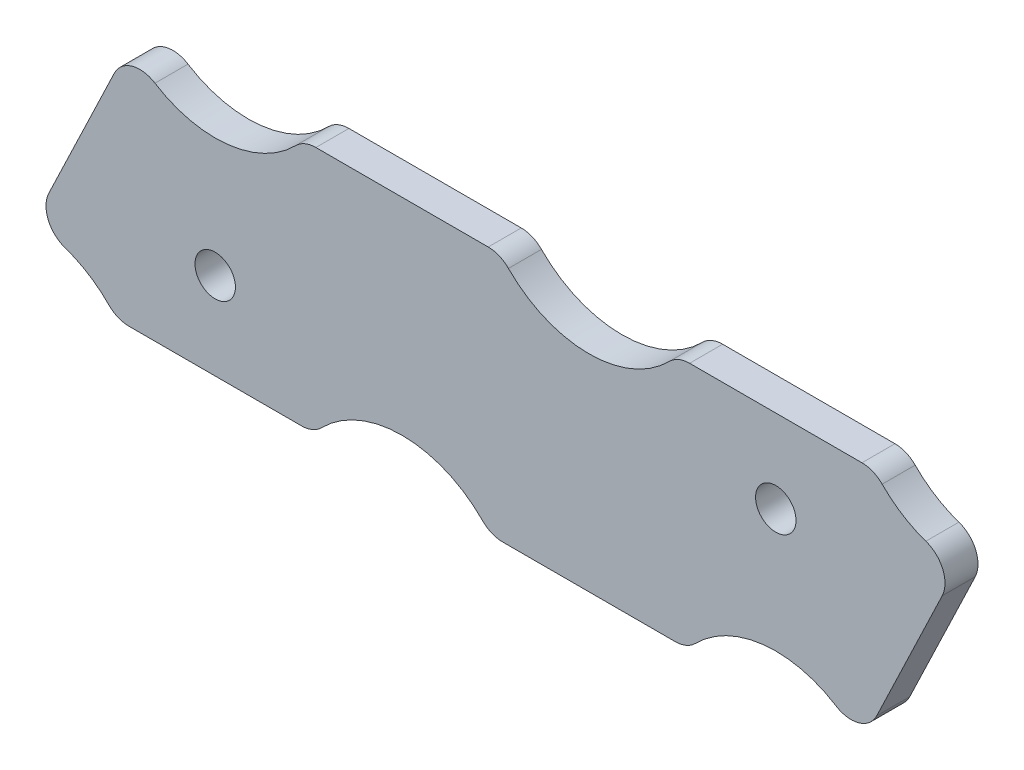
SolidWorks part; units mm, degrees
material "3003-H14"
ref_plane "X-Y Datum" through (0, 0, 0) normal (0, 0, 1) x (1, 0, 0)
ref_plane "X-Z Datum" through (0, 0, 0) normal (0, 1, 0) x (1, 0, 0)
ref_plane "Y-Z Datum" through (0, 0, 0) normal (1, 0, 0) x (0, 0, -1)
sketch "Sketch3" plane through (0, 0, 0) normal (0, 0, 1) x (1, 0, 0)
  line L0 (10.775, 10.775) -> (22.275, 34.775) construction
  line L1 (0, 0) -> (156.4633, 0) construction
  line L2 (0, 0) -> (0, 56.3098) construction
  line L3 (0, 56.3098) -> (156.4633, 56.3098) construction
  line L4 (156.4633, 0) -> (156.4633, 56.3098) construction
  line L5 (33.775, 10.775) -> (45.275, 34.775) construction
  line L6 (56.775, 10.775) -> (68.275, 34.775) construction
  line L7 (16.525, 22.775) -> (62.525, 22.775) construction
  line L8 (33.775, 10.775) -> (22.275, 34.775) construction
  line L9 (45.275, 34.775) -> (56.775, 10.775) construction
  line L10 (10.775, 10.775) -> (33.775, 10.775) construction
  line L11 (56.775, 10.775) -> (33.775, 10.775) construction
  line L12 (22.275, 34.775) -> (45.275, 34.775) construction
  line L13 (68.275, 34.775) -> (45.275, 34.775) construction
  line L14 (22.275, 34.775) -> (22.275, 10.775) construction
  line L15 (45.275, 10.775) -> (45.275, 34.775) construction
  line L16 (33.775, 10.775) -> (33.775, 34.775) construction
  line L17 (56.775, 34.775) -> (56.775, 10.775) construction
  line L18 (13.4804, 9.4786) -> (24.9804, 33.4786)
  line L19 (36.4804, 9.4786) -> (47.9804, 33.4786)
  line L20 (59.4804, 9.4786) -> (70.9804, 33.4786)
  line L21 (8.0696, 12.0714) -> (19.5696, 36.0714)
  line L22 (31.0696, 12.0714) -> (42.5696, 36.0714)
  line L23 (54.0696, 12.0714) -> (65.5696, 36.0714)
  line L24 (17.8152, 18.525) -> (57.1619, 18.525)
  line L25 (21.8881, 27.025) -> (61.2348, 27.025)
  line L26 (16.525, 27.025) -> (62.525, 27.025) construction
  line L27 (16.525, 18.525) -> (62.525, 18.525) construction
  line L28 (16.0692, 14.8813) -> (28.4808, 14.8813)
  line L29 (39.9808, 30.6687) -> (27.5692, 30.6687)
  line L48 (56.775, 10.775) -> (68.275, 10.775) construction
  line L49 (68.275, 10.775) -> (68.275, 34.775) construction
  line L50 (62.9808, 30.6687) -> (50.5692, 30.6687)
  line L51 (39.0692, 14.8813) -> (51.4808, 14.8813)
  circle A0 centre (10.775, 10.775) radius 10.775 construction
  circle A1 centre (33.775, 10.775) radius 10.775 construction
  circle A2 centre (22.275, 34.775) radius 10.775 construction
  circle A3 centre (45.275, 34.775) radius 10.775 construction
  circle A4 centre (68.275, 34.775) radius 10.775 construction
  circle A5 centre (56.775, 10.775) radius 10.775 construction
  circle A6 centre (10.775, 10.775) radius 4.7 construction
  circle A7 centre (33.775, 10.775) radius 4.7 construction
  circle A8 centre (56.775, 10.775) radius 4.7 construction
  circle A9 centre (68.275, 34.775) radius 4.7 construction
  circle A10 centre (45.275, 34.775) radius 4.7 construction
  circle A11 centre (22.275, 34.775) radius 4.7 construction
  circle A12 centre (22.275, 34.775) radius 6.7
  circle A13 centre (10.775, 10.775) radius 6.7
  circle A14 centre (33.775, 10.775) radius 6.7
  circle A15 centre (45.275, 34.775) radius 6.7
  circle A16 centre (68.275, 34.775) radius 6.7
  circle A17 centre (56.775, 10.775) radius 6.7
  circle A18 centre (125.775, 10.775) radius 10.775 construction
  circle A19 centre (102.775, 10.775) radius 10.775 construction
  circle A20 centre (79.775, 10.775) radius 10.775 construction
  circle A21 centre (91.275, 34.775) radius 10.775 construction
  circle A22 centre (114.275, 34.775) radius 10.775 construction
  circle A23 centre (137.275, 34.775) radius 10.775 construction
  dimension "D1" = 21.55
  dimension "D9" = 9.4
  dimension "D2" = 23
  dimension "D3" = 24
  dimension "D4" = 11.5
  dimension "D6" = 23
  dimension "D8" = 23
  dimension "D10" = 3
  dimension "D11" = 3
  dimension "D12" = 4.25
  dimension "D13" = 4.25
  dimension "D14" = 2
  dimension "D5" = 6
  dimension "D7" = 5
extrude "Boss-Extrude1" add sketch "Sketch3" along normal blind 2.032 contours L17 | L17 | L17 | L17 | L49 | A13 L18 A12 L21 | L25 L18 L24 L22 | L25 L22 L24 L19 | L25 L19 L24 L23 | A17 L20 A16 L23 | A14 L19 L24 L22 | A15 L22 L25 L19 | A14 L22 L24 L18 L28 | A12 L18 L25 L22 L29 | A17 L23 L24 L19 L51 | A15 L19 L25 L23 L50 region at (16.525, 22.775, 0) region at (24.1977, 16.8116, 0) region at (28.025, 22.775, 0) region at (31.8523, 28.7384, 0) region at (37.7051, 17.4114, 0) region at (39.525, 22.775, 0) region at (41.3449, 28.1386, 0) region at (47.1977, 16.8116, 0) region at (51.025, 22.775, 0) region at (54.8523, 28.7384, 0) region at (62.525, 22.775, 0)
ref_plane "Plane1" through (68.275, 0, 0) normal (1, 0, 0) x (0, 0, -1)
fillet "Fillet1" radius 2 12 edges at (62.9808, 30.6687, 1.016) (50.5692, 30.6687, 1.016) (39.9808, 30.6687, 1.016) (27.5692, 30.6687, 1.016) (16.0692, 14.8813, 1.016) (28.4808, 14.8813, 1.016) (39.0692, 14.8813, 1.016) (51.4808, 14.8813, 1.016) (68.3917, 28.076, 1.016) (62.0692, 14.8813, 1.016) (10.6583, 17.474, 1.016) (16.9808, 30.6687, 1.016)
sketch "Sketch4" plane through (0, 0, 2.032) normal (0, 0, 1) x (1, 0, 0)
  circle A0 centre (22.275, 20.4921) radius 1.2446
  circle A1 centre (56.775, 25.307) radius 1.2446
  point P0 (56.775, 25.307)
  point P1 (22.275, 20.4921)
  dimension "D1" = 2.4892
extrude "Cut-Extrude1" cut sketch "Sketch4" against normal through all
sketch "Sketch5" [suppressed] plane through (0, 0, 2.032) normal (0, 0, 1) x (1, 0, 0)
  line L0 (13.8196, 24.0714) -> (66.4728, 24.0714)
  line L1 (11.8041, 19.8652) -> (15.835, 28.2776) construction
  line L2 (63.215, 17.2724) -> (67.2459, 25.6848) construction
  line L3 (65.2304, 21.4786) -> (12.5772, 21.4786)
  line L5 (40.1462, 24.0714) -> (40.1462, 21.4786)
  line L6 (38.9038, 21.4786) -> (38.9038, 24.0714)
  line L7 (38.9038, 22.775) -> (40.1462, 22.775)
  line L9 (16.025, 27.275) -> (63.025, 27.275)
  line L10 (16.025, 27.275) -> (16.025, 18.275)
  line L11 (16.025, 18.275) -> (63.025, 18.275)
  line L12 (63.025, 27.275) -> (63.025, 18.275)
  line L13 (16.025, 27.275) -> (63.025, 18.275) construction
  line L14 (16.025, 18.275) -> (63.025, 27.275) construction
  point P11 (40.1462, 24.0714)
  point P15 (39.525, 22.775)
  dimension "D1" = 47
  dimension "D2" = 9
sketch "Sketch6" plane through (0, 0, 2.032) normal (0, 0, 1) x (1, 0, 0)
  line L0 (16.0641, 28.1678) -> (12.0331, 19.7554)
  line L1 (16.9721, 15.1353) -> (27.5779, 15.1353)
  line L2 (39.9721, 15.1353) -> (50.5779, 15.1353)
  line L3 (62.9859, 17.3822) -> (67.0169, 25.7946)
  line L4 (62.0779, 30.4147) -> (51.4721, 30.4147)
  line L5 (39.0779, 30.4147) -> (28.4721, 30.4147)
  line L6 (62.0779, 30.6687) -> (51.4721, 30.6687)
  line L7 (39.0779, 30.6687) -> (28.4721, 30.6687)
  line L8 (15.835, 28.2776) -> (11.8041, 19.8652)
  line L9 (16.9721, 14.8813) -> (27.5779, 14.8813)
  line L10 (39.9721, 14.8813) -> (50.5779, 14.8813)
  line L11 (63.215, 17.2724) -> (67.2459, 25.6848)
  line L12 (62.0779, 30.6687) -> (51.4721, 30.6687)
  line L13 (39.0779, 30.6687) -> (28.4721, 30.6687)
  line L14 (15.835, 28.2776) -> (11.8041, 19.8652)
  line L15 (16.9721, 14.8813) -> (27.5779, 14.8813)
  line L16 (39.9721, 14.8813) -> (50.5779, 14.8813)
  line L17 (63.215, 17.2724) -> (67.2459, 25.6848)
  arc A0 (12.0331, 19.7554) -> (13.0392, 17.3501) centre (13.6077, 19.0009) ccw
  arc A1 (15.7284, 15.6558) -> (13.0392, 17.3501) centre (10.775, 10.775) ccw
  arc A2 (15.7284, 15.6558) -> (16.9721, 15.1353) centre (16.9721, 16.8813) ccw
  arc A3 (27.5779, 15.1353) -> (28.8216, 15.6558) centre (27.5779, 16.8813) ccw
  arc A4 (38.7284, 15.6558) -> (28.8216, 15.6558) centre (33.775, 10.775) ccw
  arc A5 (38.7284, 15.6558) -> (39.9721, 15.1353) centre (39.9721, 16.8813) ccw
  arc A6 (50.5779, 15.1353) -> (51.8216, 15.6558) centre (50.5779, 16.8813) ccw
  arc A7 (60.4809, 16.6593) -> (51.8216, 15.6558) centre (56.775, 10.775) ccw
  arc A8 (60.4809, 16.6593) -> (62.9859, 17.3822) centre (61.4113, 18.1367) ccw
  arc A9 (67.0169, 25.7946) -> (66.0108, 28.1999) centre (65.4423, 26.5491) ccw
  arc A10 (63.3216, 29.8942) -> (66.0108, 28.1999) centre (68.275, 34.775) ccw
  arc A11 (63.3216, 29.8942) -> (62.0779, 30.4147) centre (62.0779, 28.6687) ccw
  arc A12 (51.4721, 30.4147) -> (50.2284, 29.8942) centre (51.4721, 28.6687) ccw
  arc A13 (40.3216, 29.8942) -> (50.2284, 29.8942) centre (45.275, 34.775) ccw
  arc A14 (40.3216, 29.8942) -> (39.0779, 30.4147) centre (39.0779, 28.6687) ccw
  arc A15 (28.4721, 30.4147) -> (27.2284, 29.8942) centre (28.4721, 28.6687) ccw
  arc A16 (18.5691, 28.8907) -> (27.2284, 29.8942) centre (22.275, 34.775) ccw
  arc A17 (18.5691, 28.8907) -> (16.0641, 28.1678) centre (17.6387, 27.4133) ccw
  arc A18 (63.5026, 30.0725) -> (66.0935, 28.4401) centre (68.275, 34.775) ccw
  arc A19 (63.5026, 30.0725) -> (62.0779, 30.6687) centre (62.0779, 28.6687) ccw
  arc A20 (51.4721, 30.6687) -> (50.0474, 30.0725) centre (51.4721, 28.6687) ccw
  arc A21 (40.5026, 30.0725) -> (50.0474, 30.0725) centre (45.275, 34.775) ccw
  arc A22 (40.5026, 30.0725) -> (39.0779, 30.6687) centre (39.0779, 28.6687) ccw
  arc A23 (28.4721, 30.6687) -> (27.0474, 30.0725) centre (28.4721, 28.6687) ccw
  arc A24 (18.7045, 29.1057) -> (27.0474, 30.0725) centre (22.275, 34.775) ccw
  arc A25 (18.7045, 29.1057) -> (15.835, 28.2776) centre (17.6387, 27.4133) ccw
  arc A26 (11.8041, 19.8652) -> (12.9565, 17.1099) centre (13.6077, 19.0009) ccw
  arc A27 (15.5474, 15.4775) -> (12.9565, 17.1099) centre (10.775, 10.775) ccw
  arc A28 (15.5474, 15.4775) -> (16.9721, 14.8813) centre (16.9721, 16.8813) ccw
  arc A29 (27.5779, 14.8813) -> (29.0026, 15.4775) centre (27.5779, 16.8813) ccw
  arc A30 (38.5474, 15.4775) -> (29.0026, 15.4775) centre (33.775, 10.775) ccw
  arc A31 (38.5474, 15.4775) -> (39.9721, 14.8813) centre (39.9721, 16.8813) ccw
  arc A32 (50.5779, 14.8813) -> (52.0026, 15.4775) centre (50.5779, 16.8813) ccw
  arc A33 (60.3455, 16.4443) -> (52.0026, 15.4775) centre (56.775, 10.775) ccw
  arc A34 (60.3455, 16.4443) -> (63.215, 17.2724) centre (61.4113, 18.1367) ccw
  arc A35 (67.2459, 25.6848) -> (66.0935, 28.4401) centre (65.4423, 26.5491) ccw
  arc A36 (63.5026, 30.0725) -> (66.0935, 28.4401) centre (68.275, 34.775) ccw
  arc A37 (63.5026, 30.0725) -> (62.0779, 30.6687) centre (62.0779, 28.6687) ccw
  arc A38 (51.4721, 30.6687) -> (50.0474, 30.0725) centre (51.4721, 28.6687) ccw
  arc A39 (40.5026, 30.0725) -> (50.0474, 30.0725) centre (45.275, 34.775) ccw
  arc A40 (40.5026, 30.0725) -> (39.0779, 30.6687) centre (39.0779, 28.6687) ccw
  arc A41 (28.4721, 30.6687) -> (27.0474, 30.0725) centre (28.4721, 28.6687) ccw
  arc A42 (18.7045, 29.1057) -> (27.0474, 30.0725) centre (22.275, 34.775) ccw
  arc A43 (18.7045, 29.1057) -> (15.835, 28.2776) centre (17.6387, 27.4133) ccw
  arc A44 (11.8041, 19.8652) -> (12.9565, 17.1099) centre (13.6077, 19.0009) ccw
  arc A45 (15.5474, 15.4775) -> (12.9565, 17.1099) centre (10.775, 10.775) ccw
  arc A46 (15.5474, 15.4775) -> (16.9721, 14.8813) centre (16.9721, 16.8813) ccw
  arc A47 (27.5779, 14.8813) -> (29.0026, 15.4775) centre (27.5779, 16.8813) ccw
  arc A48 (38.5474, 15.4775) -> (29.0026, 15.4775) centre (33.775, 10.775) ccw
  arc A49 (38.5474, 15.4775) -> (39.9721, 14.8813) centre (39.9721, 16.8813) ccw
  arc A50 (50.5779, 14.8813) -> (52.0026, 15.4775) centre (50.5779, 16.8813) ccw
  arc A51 (60.3455, 16.4443) -> (52.0026, 15.4775) centre (56.775, 10.775) ccw
  arc A52 (60.3455, 16.4443) -> (63.215, 17.2724) centre (61.4113, 18.1367) ccw
  arc A53 (67.2459, 25.6848) -> (66.0935, 28.4401) centre (65.4423, 26.5491) ccw
  dimension "D1" = 0
  dimension "D2" = 0.254
extrude "Cut-Extrude2" cut sketch "Sketch6" against normal through all
